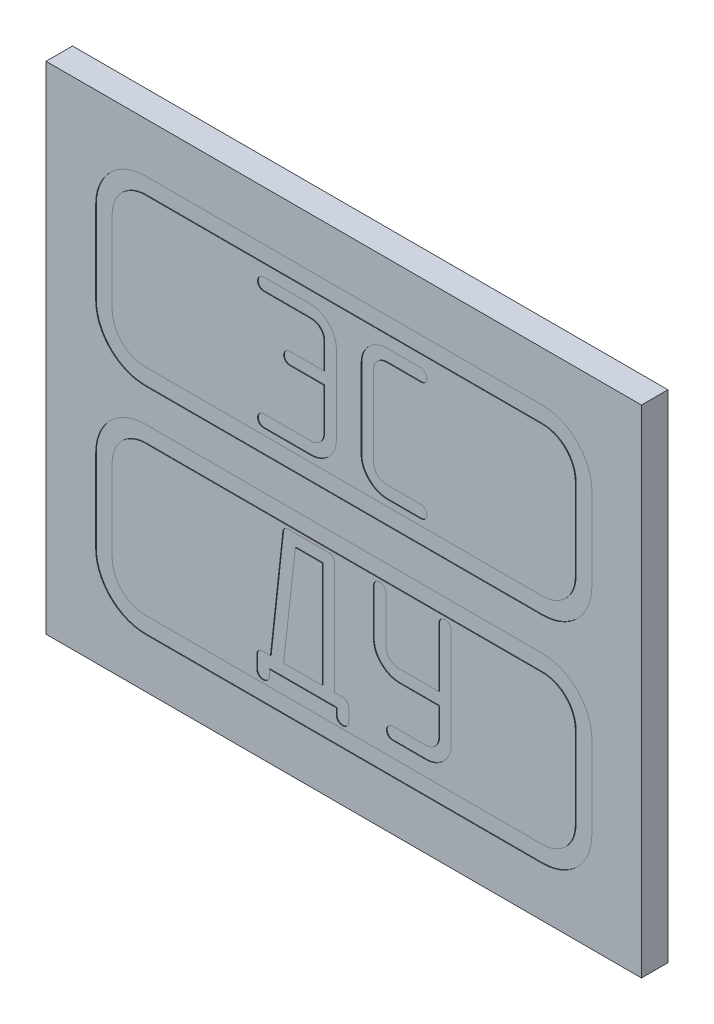
SolidWorks part; units mm, degrees
ref_plane "Спереди" through (0, 0, 0) normal (0, 0, 1) x (1, 0, 0)
ref_plane "Сверху" through (0, 0, 0) normal (0, 1, 0) x (1, 0, 0)
ref_plane "Справа" through (0, 0, 0) normal (1, 0, 0) x (0, 0, -1)
sketch "Эскиз1" plane through (0, 0, 0) normal (0, 0, 1) x (1, 0, 0)
  line L0 (-39.1383, 0) -> (46.6595, 0) construction
  line L1 (0, 30.7814) -> (0, -28.8314) construction
  line L3 (-9, -7.5) -> (9, -7.5)
  line L4 (-9, -7.5) -> (-9, 7.5)
  line L5 (-9, 7.5) -> (9, 7.5)
  line L6 (9, -7.5) -> (9, 7.5)
  dimension "D1" = 18
  dimension "D2" = 15
extrude "Вытянуть1" add sketch "Эскиз1" along normal blind 0.8
sketch "Эскиз2" plane through (0, 0, 0.8) normal (0, 0, 1) x (1, 0, 0)
  line L0 (-9, -7.5) -> (9, -7.5) construction
  line L1 (-6, 1) -> (6, 1)
  line L2 (-7, 2) -> (-7, 4.5)
  line L3 (-6, 5.5) -> (6, 5.5)
  line L4 (7, 2) -> (7, 4.5)
  line L9 (-9, 7.5) -> (-9, -7.5) construction
  line L10 (9, -7.5) -> (9, 7.5) construction
  arc A0 (-7, 4.5) -> (-6, 5.5) centre (-6, 4.5) cw
  arc A1 (6, 5.5) -> (7, 4.5) centre (6, 4.5) cw
  arc A2 (6, 1) -> (7, 2) centre (6, 2) ccw
  arc A3 (-6, 1) -> (-7, 2) centre (-6, 2) cw
  dimension "D7" = 1
  dimension "D1" = 8.5
  dimension "D5" = 13
  dimension "D6" = 2
  dimension "D8" = 2
extrude "Вырез-Вытянуть-Тонкостенный1" cut sketch "Эскиз2" against normal blind 0.02 and the other way blind 0.02 thin thin type one direction wall 0.5
sketch "Эскиз3" plane through (0, 0, 0.8) normal (0, 0, 1) x (1, 0, 0)
  line L2 (-9, 7.5) -> (-9, -7.5) construction
  text T0 "ЭС" font "GOST type B" height 4
  text T1 "ДУ" font "GOST type B" height 4
  dimension "D1" = 6
extrude "Вырез-Вытянуть1" cut sketch "Эскиз3" against normal blind 0.02
sketch "Эскиз4" plane through (0, 0, 0.8) normal (0, 0, 1) x (1, 0, 0)
  line L0 (-9, 7.5) -> (-9, -7.5) construction
  line L1 (-6, -5.5) -> (6, -5.5)
  line L2 (-7, -4.5) -> (-7, -2)
  line L3 (-6, -1) -> (6, -1)
  line L4 (7, -4.5) -> (7, -2)
  line L5 (9, -7.5) -> (9, 7.5) construction
  line L6 (-9, -7.5) -> (9, -7.5) construction
  arc A0 (-7, -2) -> (-6, -1) centre (-6, -2) cw
  arc A1 (-6, -5.5) -> (-7, -4.5) centre (-6, -4.5) cw
  arc A2 (6, -1) -> (7, -2) centre (6, -2) cw
  arc A3 (6, -5.5) -> (7, -4.5) centre (6, -4.5) ccw
  point P16 (7, -1)
  point P19 (7, -5.5)
  dimension "D5" = 1
  dimension "D1" = 2
  dimension "D2" = 2
  dimension "D3" = 2
  dimension "D4" = 4.5
extrude "Вырез-Вытянуть-Тонкостенный2" cut sketch "Эскиз4" against normal blind 0.02 and the other way blind 0.02 thin thin type one direction wall 0.5
